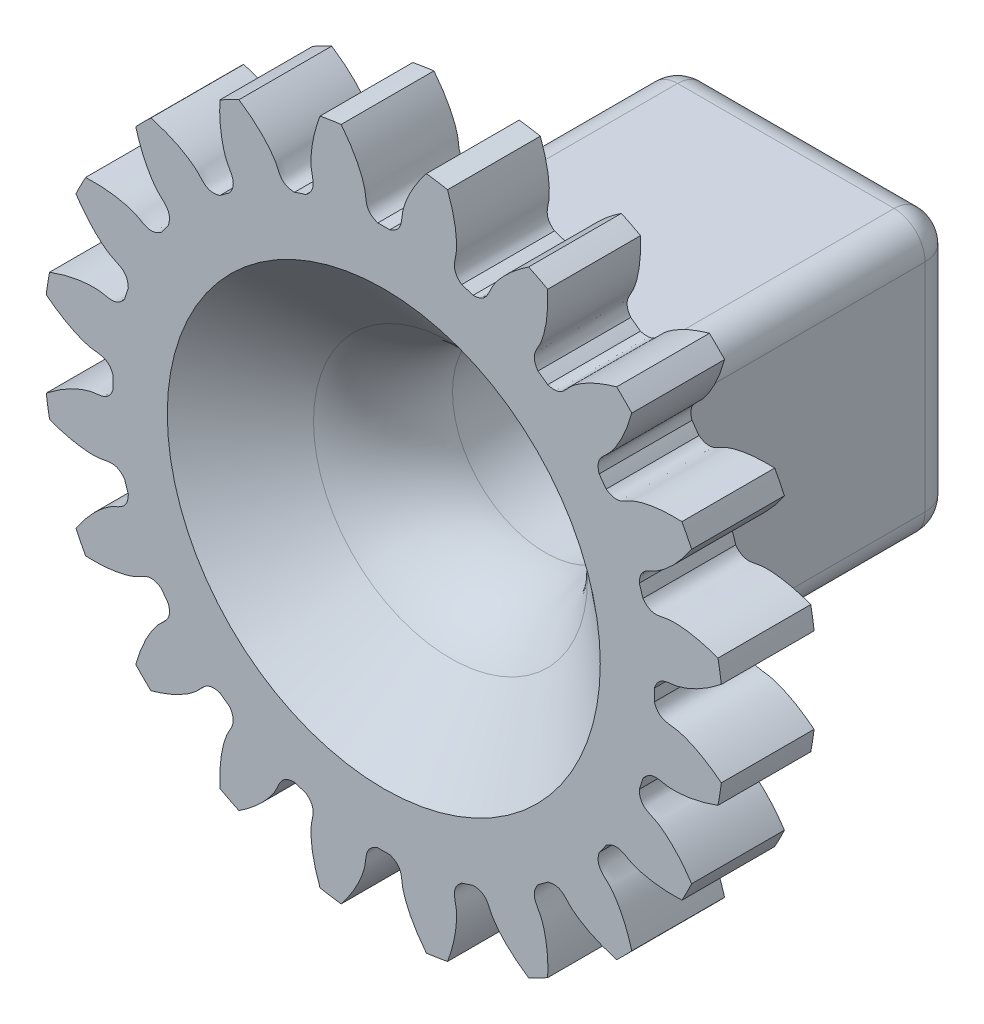
SolidWorks part; units mm, degrees
ref_plane "前视基准面" through (0, 0, 0) normal (0, 0, 1) x (1, 0, 0)
ref_plane "上视基准面" through (0, 0, 0) normal (0, 1, 0) x (1, 0, 0)
ref_plane "右视基准面" through (0, 0, 0) normal (1, 0, 0) x (0, 0, -1)
sketch "草图1" plane through (0, 0, 0) normal (0, 0, 1) x (1, 0, 0)
  circle A0 centre (0, 0) radius 11
extrude "凸台-拉伸1" add sketch "草图1" along normal blind 3
ref_axis "基准轴1" through (0, 0, -1.5) along (0, 0, 1)
sketch "草图2" plane through (0, 0, 0) normal (0, 0, 1) x (1, 0, 0)
  line L0 (0, 0) -> (0, 11) construction
  circle A0 centre (0, 0) radius 11 construction
  arc A1 (0.1933, 8.7479) -> (-0.1933, 8.7479) centre (0, 0) ccw
  arc A2 (3.1812, 12.4983) -> (-3.1812, 12.4983) centre (0, 0) ccw
  spline S0 degree 3 poles (0.1933, 8.7479) (0.6112, 8.8935) (0.5571, 9.1871) (0.6129, 9.47) (0.6189, 9.4976) (0.6263, 9.5286) (0.6353, 9.5632) (0.646, 9.6012) (0.6585, 9.6426) (0.673, 9.6873) (0.6897, 9.7352) (0.7086, 9.7863) (0.7299, 9.8406) (0.7537, 9.8978) (0.7801, 9.958) (0.8094, 10.0211) (0.8415, 10.087) (0.8767, 10.1556) (0.915, 10.2267) (0.9566, 10.3004) (1.0015, 10.3764) (1.05, 10.4548) (1.102, 10.5352) (1.1578, 10.6178) (1.2173, 10.7023) (1.2808, 10.7886) (1.3482, 10.8766) (1.4198, 10.9662) (1.4955, 11.0572) (1.5755, 11.1496) (1.6598, 11.2431) (1.7486, 11.3376) (1.8418, 11.4331) (1.9397, 11.5293) (2.0421, 11.6261) (2.1493, 11.7233) (2.2612, 11.8209) (2.378, 11.9186) (2.4996, 12.0163) (2.6261, 12.1139) (2.7575, 12.2112) (2.9415, 12.3416) (3.0839, 12.4363) (3.1812, 12.4983) knots 0 0 0 0 0.165916 0.170906 0.176664 0.183189 0.190482 0.198542 0.207371 0.216967 0.22733 0.238462 0.250361 0.263027 0.276462 0.290664 0.305634 0.321371 0.337876 0.355149 0.37319 0.391998 0.411574 0.431917 0.453028 0.474907 0.497554 0.520968 0.54515 0.570099 0.595817 0.622302 0.649554 0.677575 0.706363 0.735918 0.766242 0.797333 0.829191 0.861818 0.895212 0.929373 1 1 1 1
  spline S1 degree 3 poles (-0.1933, 8.7479) (-0.6112, 8.8935) (-0.5571, 9.1871) (-0.6129, 9.47) (-0.6189, 9.4976) (-0.6263, 9.5286) (-0.6353, 9.5632) (-0.646, 9.6012) (-0.6585, 9.6426) (-0.673, 9.6873) (-0.6897, 9.7352) (-0.7086, 9.7863) (-0.7299, 9.8406) (-0.7537, 9.8978) (-0.7801, 9.958) (-0.8094, 10.0211) (-0.8415, 10.087) (-0.8767, 10.1556) (-0.915, 10.2267) (-0.9566, 10.3004) (-1.0015, 10.3764) (-1.05, 10.4548) (-1.102, 10.5352) (-1.1578, 10.6178) (-1.2173, 10.7023) (-1.2808, 10.7886) (-1.3482, 10.8766) (-1.4198, 10.9662) (-1.4955, 11.0572) (-1.5755, 11.1496) (-1.6598, 11.2431) (-1.7486, 11.3376) (-1.8418, 11.4331) (-1.9397, 11.5293) (-2.0421, 11.6261) (-2.1493, 11.7233) (-2.2612, 11.8209) (-2.378, 11.9186) (-2.4996, 12.0163) (-2.6261, 12.1139) (-2.7575, 12.2112) (-2.9415, 12.3416) (-3.0839, 12.4363) (-3.1812, 12.4983) knots 0 0 0 0 0.165916 0.170906 0.176664 0.183189 0.190482 0.198542 0.207371 0.216967 0.22733 0.238462 0.250361 0.263027 0.276462 0.290664 0.305634 0.321371 0.337876 0.355149 0.37319 0.391998 0.411574 0.431917 0.453028 0.474907 0.497554 0.520968 0.54515 0.570099 0.595817 0.622302 0.649554 0.677575 0.706363 0.735918 0.766242 0.797333 0.829191 0.861818 0.895212 0.929373 1 1 1 1
extrude "切除-拉伸1" cut sketch "草图2" along normal through all
pattern_circular "阵列(圆周)1" count 20 every 18 about axis through (0, 0, -1.5) along (0, 0, 1) of "切除-拉伸1"
sketch "草图3" plane through (0, 0, 0) normal (0, 0, 1) x (1, 0, 0)
  circle A0 centre (0, 0) radius 10 construction
  dimension "Dn" = 20
sketch "草图4" plane through (0, 0, 0) normal (0, 0, -1) x (-1, 0, 0)
  circle A0 centre (0, 0) radius 3
  dimension "D1" = 6
extrude "切除-拉伸2" cut sketch "草图4" against normal blind 10
sketch "草图5" plane through (0, 0, 0) normal (0, 0, -1) x (-1, 0, 0)
  line L1 (-4.5, 4.5) -> (4.5, 4.5)
  line L2 (-4.5, 4.5) -> (-4.5, -4.5)
  line L3 (-4.5, -4.5) -> (4.5, -4.5)
  line L4 (4.5, 4.5) -> (4.5, -4.5)
  line L5 (-4.5, 4.5) -> (4.5, -4.5) construction
  line L6 (-4.5, -4.5) -> (4.5, 4.5) construction
  circle A0 centre (0, 0) radius 3 construction
  circle A1 centre (0, 0) radius 3
  point P0 (0, 0)
  dimension "D1" = 9
  dimension "D2" = 9
extrude "凸台-拉伸2" add sketch "草图5" along normal blind 11
sketch "草图6" plane through (0, 0, 0) normal (0, 0, -1) x (-1, 0, 0)
  circle A0 centre (0, 0) radius 6.5
  circle A1 centre (0, 0) radius 3 construction
  circle A2 centre (0, 0) radius 3
  dimension "D1" = 13
extrude "凸台-拉伸3" add sketch "草图6" along normal blind 1
chamfer "倒角1" distance 4 angle 40 1 edges at (3, 0, 3) first distance on face at (3, 0, 3)
fillet "圆角1" radius 4 1 edges at (3, 0, -0.3564)
fillet "圆角2" radius 1 4 edges at (-4.5, -4.5, -6) (4.5, -4.5, -6) (-4.5, 4.5, -6) (4.5, 4.5, -6)
fillet "圆角3" radius 1 8 edges at (4.2071, 4.2071, -11) (0, 4.5, -11) (-4.2071, 4.2071, -11) (-4.5, 0, -11) (-4.2071, -4.2071, -11) (0, -4.5, -11) (4.2071, -4.2071, -11) (4.5, 0, -11)
